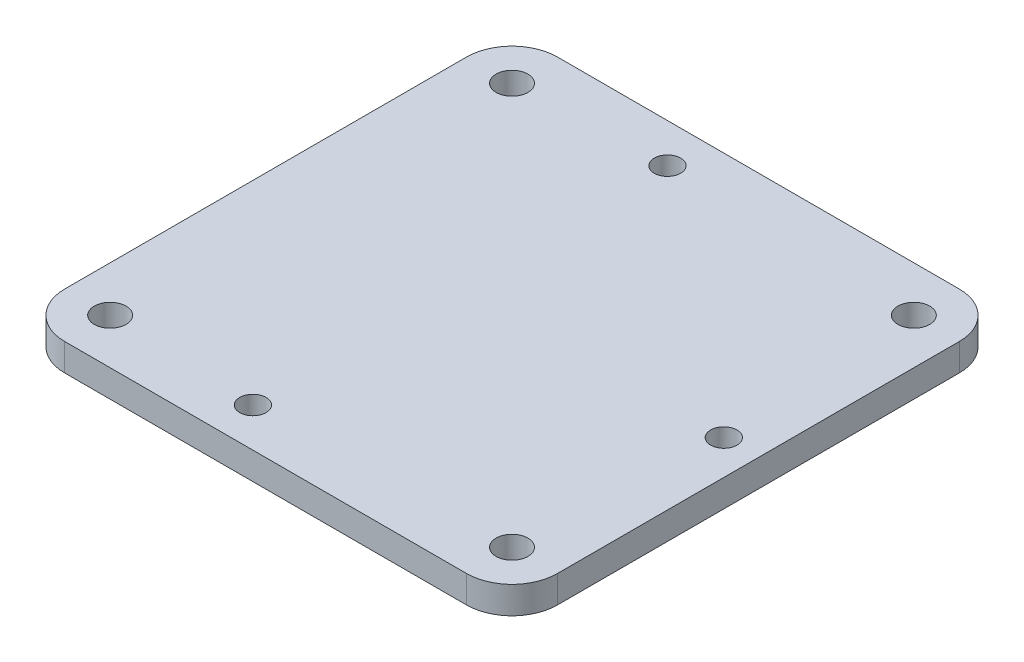
SolidWorks part; units mm, degrees
ref_plane "Front Plane" through (0, 0, 0) normal (0, 0, 1) x (1, 0, 0)
ref_plane "Top Plane" through (0, 0, 0) normal (0, 1, 0) x (1, 0, 0)
ref_plane "Right Plane" through (0, 0, 0) normal (1, 0, 0) x (0, 0, -1)
sketch "Sketch1" plane through (0, 0, 0) normal (0, 1, 0) x (1, 0, 0)
  line L0 (21.4, 49.9) -> (21.4, 4.3) construction
  line L1 (0, 0) -> (54.2, 0)
  line L2 (0, 0) -> (0, 54.2)
  line L3 (0, 54.2) -> (54.2, 54.2)
  line L4 (54.2, 0) -> (54.2, 54.2)
  line L5 (21.4, 27.1) -> (50.4, 27.1) construction
  line L6 (0, 54.2) -> (21.4, 49.9) construction
  line L7 (0, 0) -> (21.4, 4.3) construction
  line L8 (5, 49.2) -> (0, 54.2) construction
  line L9 (5, 49.2) -> (49.2, 49.2) construction
  line L10 (5, 49.2) -> (5, 5) construction
  line L11 (5, 5) -> (49.2, 5) construction
  line L12 (49.2, 49.2) -> (49.2, 5) construction
  line L13 (49.2, 49.2) -> (54.2, 54.2) construction
  line L14 (49.2, 5) -> (54.2, 0) construction
  line L15 (5, 5) -> (0, 0) construction
  circle A0 centre (21.4, 49.9) radius 1.45
  circle A1 centre (21.4, 4.3) radius 1.45
  circle A2 centre (50.4, 27.1) radius 1.45
  circle A3 centre (5, 49.2) radius 1.75
  circle A4 centre (49.2, 49.2) radius 1.75
  circle A5 centre (49.2, 5) radius 1.75
  circle A6 centre (5, 5) radius 1.75
  point P14 (53.8408, 0)
  point P18 (5.9748, 48.2252)
  point P20 (4.7733, 4.7733)
  dimension "D1" = 45.6
  dimension "D4" = 2.9
  dimension "D7" = 3.5
  dimension "D2" = 29
  dimension "D3" = 54.2
  dimension "D5" = 54.2
  dimension "D6" = 3.8
  dimension "D8" = 5
extrude "Boss-Extrude1" add sketch "Sketch1" along normal blind 3
fillet "Fillet1" radius 5 4 edges at (54.2, 1.5, -54.2) (54.2, 1.5, 0) (0, 1.5, 0) (0, 1.5, -54.2)
